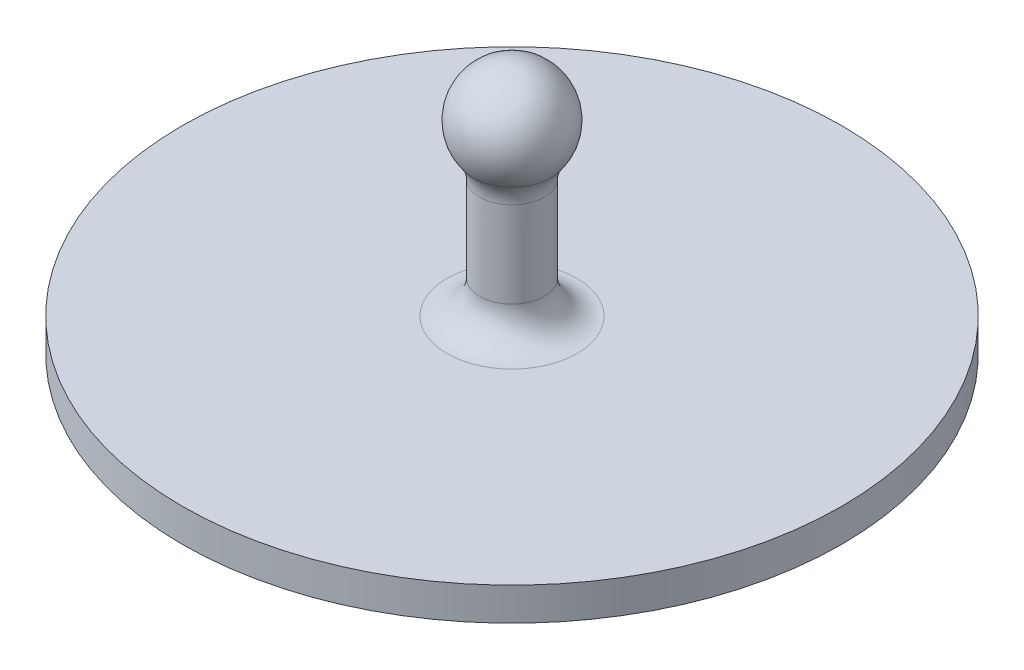
SolidWorks part; units mm, degrees
ref_plane "Alzado" through (0, 0, 0) normal (0, 0, 1) x (1, 0, 0)
ref_plane "Planta" through (0, 0, 0) normal (0, 1, 0) x (1, 0, 0)
ref_plane "Vista lateral" through (0, 0, 0) normal (1, 0, 0) x (0, 0, -1)
sketch "Croquis2" plane through (0, 0, 0) normal (0, 1, 0) x (1, 0, 0)
  circle A0 centre (0, 0) radius 1.95
  dimension "D1" = 3.9
extrude "Saliente-Extruir1" add sketch "Croquis2" along normal blind 8 contours A0
dome "Cúpula1" faces to dome 1 distance 5.3 reverse direction no elliptical dome no face at (0, 8, 1.95) parameters "D1"=5.3
sketch "Croquis15" plane through (0, 0, 0) normal (0, -1, 0) x (-1, 0, 0)
  circle A0 centre (0, 0) radius 20
  dimension "D1" = 40
extrude "Saliente-Extruir2" add sketch "Croquis15" along normal blind 2
ref_plane "Plano3" through (0, 5, 0) normal (0, 1, 0) x (1, 0, 0)
sketch "Croquis19" plane through (0, 5, 0) normal (0, 1, 0) x (1, 0, 0)
  circle A0 centre (0, 0) radius 1.975
  point P2 (0, 0)
  dimension "D1" = 3.95
fillet "Fillet1" radius 2 2 edges at (0, 8, 1.95) (0, 0, -1.95)
sketch "Sketch1" plane through (0, -2, 0) normal (0, -1, 0) x (1, 0, 0)
  circle A0 centre (0, 0) radius 19
  circle A1 centre (0, 0) radius 20
  circle A2 centre (0, 0) radius 20
  dimension "D1" = 0
  dimension "D2" = 1
extrude "Cut-Extrude1" cut sketch "Sketch1" against normal blind 0.5 contours A0 region at (0, -2, 0)
